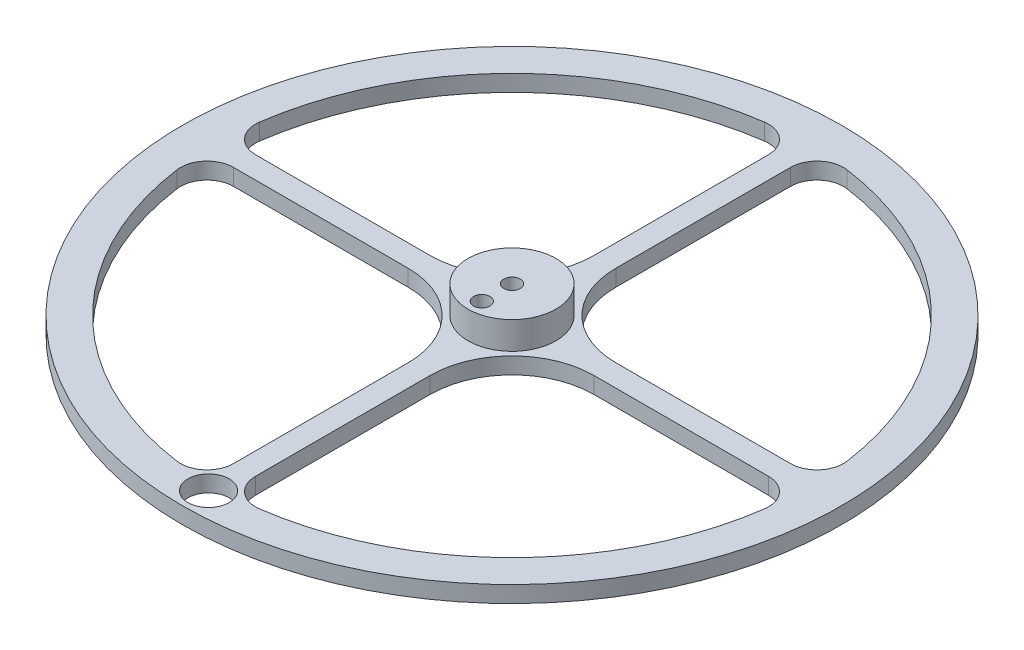
SolidWorks part; units mm, degrees
ref_plane "Front Plane" through (0, 0, 0) normal (0, 0, 1) x (1, 0, 0)
ref_plane "Top Plane" through (0, 0, 0) normal (0, 1, 0) x (1, 0, 0)
ref_plane "Right Plane" through (0, 0, 0) normal (1, 0, 0) x (0, 0, -1)
sketch "Sketch1" plane through (0, 0, 0) normal (0, 1, 0) x (1, 0, 0)
  line L0 (2, -48.6942) -> (2, -16.8995)
  line L1 (0, 0) -> (-6.364, -6.364) construction
  line L2 (0, 0) -> (6.364, -6.364) construction
  line L3 (-2, -16.8995) -> (-2, -48.6942)
  line L4 (-2, -16.8995) -> (2, -16.8995) construction
  line L5 (0, -9) -> (0, 9) construction
  line L6 (0, -60) -> (0, 9) construction
  line L7 (-16.8995, 2) -> (-48.6942, 2)
  line L8 (-48.6942, -2) -> (-16.8995, -2)
  line L9 (-11.0325, 9) -> (11.0325, 9) construction
  line L10 (0, 9) -> (0, 10.9405) construction
  line L11 (-60, 0) -> (9, 0) construction
  line L12 (0, -16.8995) -> (0, -9) construction
  line L13 (-7.5, -53.4766) -> (7.5, -53.4766) construction
  line L14 (0, -60) -> (0, -53.4766) construction
  line L15 (-53.4766, 7.5) -> (-53.4766, -7.5) construction
  line L16 (2, 16.8995) -> (2, 48.6942)
  line L17 (-2, 48.6942) -> (-2, 16.8995)
  line L18 (0, 60) -> (0, -9) construction
  line L19 (7.5, 53.4766) -> (-7.5, 53.4766) construction
  line L20 (16.8995, -2) -> (48.6942, -2)
  line L21 (48.6942, 2) -> (16.8995, 2)
  line L22 (60, 0) -> (-9, 0) construction
  line L23 (53.4766, -7.5) -> (53.4766, 7.5) construction
  circle A0 centre (0, 0) radius 60
  circle A1 centre (0, 0) radius 54
  circle A2 centre (0, 0) radius 8
  circle A3 centre (0, 0) radius 9 construction
  arc A4 (2, -16.8995) -> (6.364, -6.364) centre (16.8995, -16.8995) cw
  arc A5 (-2, -48.6942) -> (-7.5, -53.4766) centre (-6.8293, -48.6942) cw
  arc A6 (2, -48.6942) -> (7.5, -53.4766) centre (6.8293, -48.6942) ccw
  arc A7 (-16.8995, 2) -> (-6.364, 6.364) centre (-16.8995, 16.8995) ccw
  arc A8 (-48.6942, 2) -> (-53.4766, 7.5) centre (-48.6942, 6.8293) cw
  arc A9 (-48.6942, -2) -> (-53.4766, -7.5) centre (-48.6942, -6.8293) ccw
  arc A10 (-16.8995, -2) -> (-6.364, -6.364) centre (-16.8995, -16.8995) cw
  arc A11 (2, 16.8995) -> (6.364, 6.364) centre (16.8995, 16.8995) ccw
  arc A12 (2, 48.6942) -> (7.5, 53.4766) centre (6.8293, 48.6942) cw
  arc A13 (-2, -16.8995) -> (-6.364, -6.364) centre (-16.8995, -16.8995) ccw
  arc A14 (-2, 48.6942) -> (-7.5, 53.4766) centre (-6.8293, 48.6942) ccw
  arc A15 (-2, 16.8995) -> (-6.364, 6.364) centre (-16.8995, 16.8995) cw
  arc A16 (16.8995, -2) -> (6.364, -6.364) centre (16.8995, -16.8995) ccw
  arc A18 (48.6942, -2) -> (53.4766, -7.5) centre (48.6942, -6.8293) cw
  arc A19 (48.6942, 2) -> (53.4766, 7.5) centre (48.6942, 6.8293) ccw
  arc A20 (16.8995, 2) -> (6.364, 6.364) centre (16.8995, 16.8995) cw
  dimension "D1" = 6
  dimension "D5" = 16
  dimension "D9" = 120
  dimension "D3" = 18
  dimension "D6" = 45
  dimension "D7" = 4
  dimension "D2" = 69
  dimension "D4" = 4
  dimension "D10" = 15
extrude "Boss-Extrude1" add sketch "Sketch1" against normal blind 3 contours A0 A1 | A13 L3 A5 A1 A6 L0 A2 | A2 region at (2.6583, 0, 53.491) region at (-58.3029, 0, 0) region at (0, 0, 0)
extrude "Boss-Extrude2" add sketch "Sketch1<3>" along normal blind 5 contours A2 region at (0, 0, 0)
sketch "Sketch1<3>" plane through (0, 0, 0) normal (0, 1, 0) x (1, 0, 0) same geometry as "Sketch1"
sketch "Sketch2" plane through (0, 5, 0) normal (0, 1, 0) x (1, 0, 0)
  circle A0 centre (0, 0) radius 1.5
  dimension "D1" = 3
extrude "Cut-Extrude1" cut sketch "Sketch2" against normal up to next
sketch "Sketch3" plane through (0, 0, 0) normal (0, 1, 0) x (1, 0, 0)
  line L0 (0, 0) -> (0, -55.25) construction
  circle A0 centre (0, -55.25) radius 3.75
  dimension "D1" = 7.5
  dimension "D2" = 55.25
extrude "Cut-Extrude2" cut sketch "Sketch3" against normal up to next
sketch "Sketch4" plane through (0, 5, 0) normal (0, 1, 0) x (1, 0, 0)
  line L0 (0, 0) -> (0, -5.5) construction
  circle A0 centre (0, -5.5) radius 1.5
  dimension "D2" = 3
  dimension "D1" = 5.5
extrude "Cut-Extrude3" cut sketch "Sketch4" against normal up to surface (5 mm away) up to face at (0, 0, 59)
